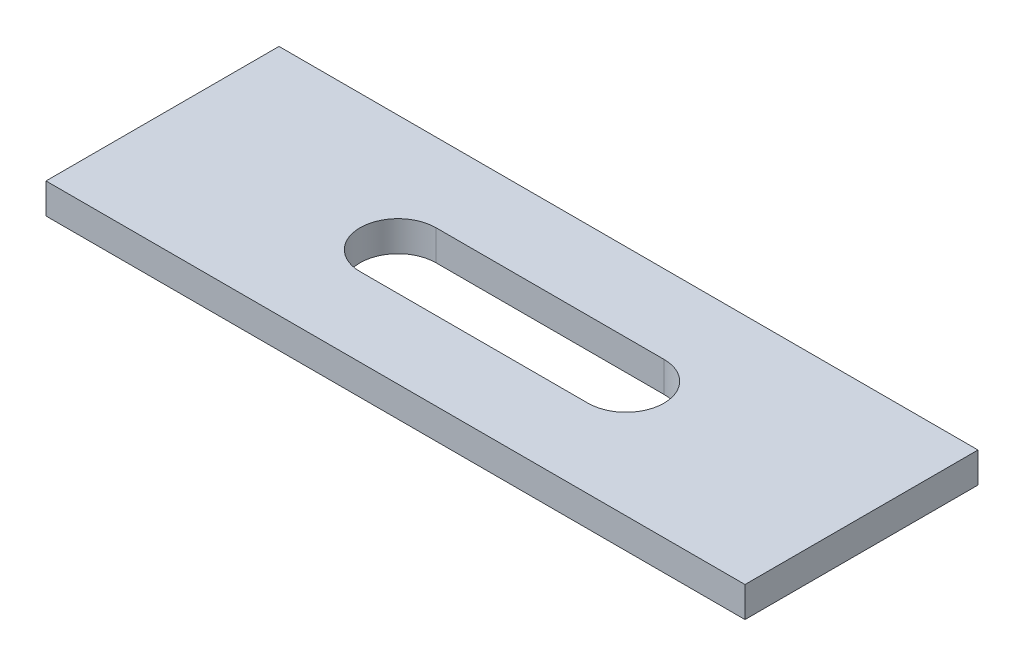
SolidWorks part; units mm, degrees
material "Pine"
ref_plane "Front Plane" through (0, 0, 0) normal (0, 0, 1) x (1, 0, 0)
ref_plane "Top Plane" through (0, 0, 0) normal (0, 1, 0) x (1, 0, 0)
ref_plane "Right Plane" through (0, 0, 0) normal (1, 0, 0) x (0, 0, -1)
sketch "Sketch2" plane through (0, 0, 0) normal (0, 1, 0) x (1, 0, 0)
  line L4 (93, 46) -> (183, 46) construction
  line L5 (0, 0) -> (276, 0)
  line L6 (0, 0) -> (0, 92)
  line L7 (0, 92) -> (276, 92)
  line L8 (276, 0) -> (276, 92)
  line L9 (93, 61) -> (183, 61)
  line L10 (93, 31) -> (183, 31)
  arc A0 (93, 61) -> (93, 31) centre (93, 46) ccw
  arc A1 (183, 31) -> (183, 61) centre (183, 46) ccw
  point P7 (138, 46)
  dimension "D3" = 46
  dimension "D5" = 15
  dimension "D1" = 92
  dimension "D2" = 276
  dimension "D4" = 93
  dimension "D6" = 90
extrude "Boss-Extrude1" add sketch "Sketch2" along normal blind 12 contours L7 L8 L5 L6
extrude "Cut-Extrude1" cut sketch "Sketch2<3>" along normal up to surface (12 mm away) contours A0 L10 A1 L9 up to face at (138, 12, -46)
sketch "Sketch2<3>" plane through (0, 0, 0) normal (0, 1, 0) x (1, 0, 0) same geometry as "Sketch2"
equation "\"LENGTH\" = 1000mm"
equation "\"PLY\"= 12mm"
equation "\"D1@Boss-Extrude1\"=\"PLY\""
